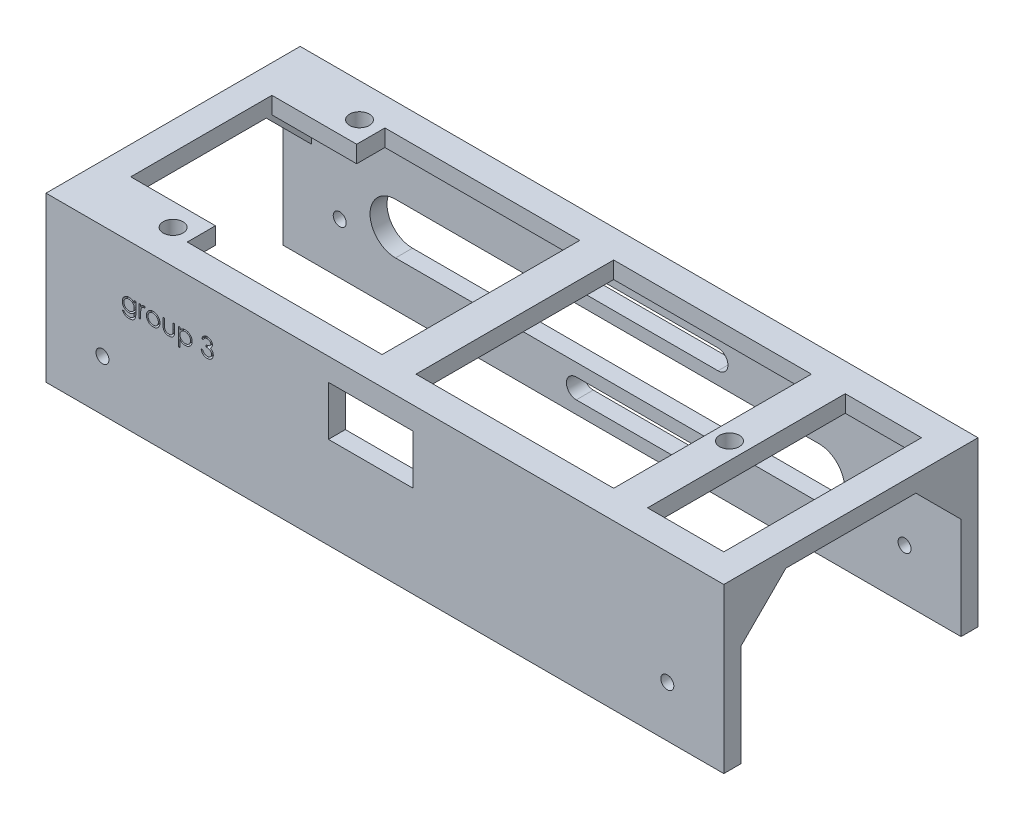
SolidWorks part; units mm, degrees
other "Markup1"
sketch "Sketch23" plane through (120, 29, 45) normal (0.0467, 0.9512, 0.3049) x (0.9885, 0, -0.1514)
sketch "Sketch24" plane through (120, 29, 45) normal (0.0467, 0.9512, 0.3049) x (0.9885, 0, -0.1514)
sketch "Sketch25" plane through (120, 29, 45) normal (0.0467, 0.9512, 0.3049) x (0.9885, 0, -0.1514)
sketch "Sketch26" plane through (120, 29, 45) normal (0.0467, 0.9512, 0.3049) x (0.9885, 0, -0.1514)
ref_plane "Front Plane" through (0, 0, 0) normal (0, 0, 1) x (1, 0, 0)
ref_plane "Top Plane" through (0, 0, 0) normal (0, 1, 0) x (1, 0, 0)
ref_plane "Right Plane" through (0, 0, 0) normal (1, 0, 0) x (0, 0, -1)
sketch "Sketch1" plane through (0, 0, 0) normal (0, 0, 1) x (1, 0, 0)
  line L9 (21.172, -17.9478) -> (91.172, -17.9478)
  line L10 (21.172, -17.9478) -> (21.172, -40.3878)
  line L11 (4, -8) -> (200.227, -8) construction
  line L12 (4, -8) -> (-67.5185, -8) construction
  line L13 (21.172, -40.3878) -> (91.172, -40.3878)
  line L14 (91.172, -17.9478) -> (91.172, -40.3878)
  line L15 (0, 0) -> (120, 0)
  line L16 (0, 0) -> (0, 29)
  line L17 (0, 29) -> (120, 29)
  line L18 (120, 0) -> (120, 29)
  circle A0 centre (4, 7) radius 1.15
  circle A1 centre (4, 7) radius 15 construction
  circle A3 centre (77.172, -29.1678) radius 3.6067
  circle A4 centre (116, 7) radius 15 construction
  circle A5 centre (116, 7) radius 1.15
  point P19 (21.172, -29.1678)
  dimension "D4" = 30
  dimension "D2" = 14
  dimension "D7" = 30
  dimension "D11" = 4
  dimension "D13" = 2.3
  dimension "D14" = 2.3
  dimension "D3" = 70
  dimension "D5" = 22.44
  dimension "D6" = 120
  dimension "D8" = 29
  dimension "D9" = 4
  dimension "D10" = 7
  dimension "D12" = 7
extrude "Boss-Extrude5" add sketch "Sketch1" along normal blind 45 contours L16 L15 L18 L17
shell "Shell9" thickness 3 removed face at (120, 14.5, 22.5) removed face at (60, 0, 22.5) removed face at (0, 14.5, 22.5)
sketch "Sketch3" plane through (0, 0, 0) normal (0, 0, -1) x (-1, 0, 0)
  line L0 (0, 0) -> (-120, 0) construction
  line L1 (-120, 0) -> (-120, 29) construction
  line L2 (0, 0) -> (0, 29) construction
  circle A0 centre (-10, 9) radius 1.15
  circle A1 centre (-110, 9) radius 1.15
  dimension "D1" = 2.3
  dimension "D2" = 2.3
  dimension "D3" = 9
  dimension "D4" = 10
  dimension "D5" = 9
  dimension "D6" = 10
extrude "Cut-Extrude2" cut sketch "Sketch3" against normal blind 79
sketch "Sketch6" plane through (0, 0, 0) normal (0, 0, -1) x (-1, 0, 0)
  line L0 (-76.9735, 21) -> (-51.8835, 21) construction
  line L1 (-76.9735, 22.75) -> (-51.8835, 22.75)
  line L2 (-76.9735, 19.25) -> (-51.8835, 19.25)
  line L7 (41.5249, -18.7743) -> (41.5249, -41.2143) construction
  line L8 (-94.8735, 12.5) -> (-19.8735, 12.5) construction
  line L9 (-94.8735, 17) -> (-19.8735, 17)
  line L10 (-94.8735, 8) -> (-19.8735, 8)
  line L11 (-19.8735, 12.5) -> (-17.326, 12.5) construction
  line L12 (-76.9735, 4) -> (-51.8835, 4) construction
  line L13 (-76.9735, 2.25) -> (-51.8835, 2.25)
  line L14 (-76.9735, 5.75) -> (-51.8835, 5.75)
  line L15 (4.7849, -29.9943) -> (74.7849, -29.9943) construction
  line L20 (4.7849, -18.7743) -> (74.7849, -18.7743)
  line L21 (4.7849, -18.7743) -> (4.7849, -41.2143)
  line L22 (4.7849, -41.2143) -> (74.7849, -41.2143)
  line L23 (74.7849, -18.7743) -> (74.7849, -41.2143)
  line L24 (-120, 0) -> (-120, 29) construction
  line L25 (63.3749, -18.7743) -> (63.3749, -41.2143) construction
  line L26 (0, 29) -> (-120, 29) construction
  arc A4 (-94.8735, 17) -> (-94.8735, 8) centre (-94.8735, 12.5) ccw
  arc A5 (-76.9735, 22.75) -> (-76.9735, 19.25) centre (-76.9735, 21) ccw
  arc A6 (-51.8835, 19.25) -> (-51.8835, 22.75) centre (-51.8835, 21) ccw
  arc A7 (-19.8735, 8) -> (-19.8735, 17) centre (-19.8735, 12.5) ccw
  arc A8 (-76.9735, 2.25) -> (-76.9735, 5.75) centre (-76.9735, 4) cw
  arc A9 (-51.8835, 5.75) -> (-51.8835, 2.25) centre (-51.8835, 4) cw
  circle A15 centre (16.1349, -29.9943) radius 1.5
  circle A16 centre (36.3249, -21.4943) radius 1.5
  circle A17 centre (36.3249, -38.4943) radius 1.5
  circle A18 centre (36.3249, -38.4943) radius 1.5
  circle A19 centre (27.0349, -29.9943) radius 2.3201
  point P11 (-64.4285, 21)
  point P19 (-57.3735, 12.5)
  point P31 (-64.4285, 4)
  dimension "D8" = 1.75
  dimension "D13" = 4.5
  dimension "D10" = 3
  dimension "D14" = 3
  dimension "D9" = 25.09
  dimension "D2" = 8.5
  dimension "D3" = 17.9
  dimension "D4" = 70
  dimension "D5" = 22.44
  dimension "D6" = 36.74
  dimension "D7" = 11.35
  dimension "D11" = 5.2
  dimension "D12" = 8.5
  dimension "D15" = 22.25
  dimension "D16" = 75
  dimension "D17" = 25.1265
  dimension "D18" = 11.41
  dimension "D19" = 16.5
extrude "Cut-Extrude8" cut sketch "Sketch6" against normal blind 23 contours L10 A7 L9 | L2 A6 L1 A5 | L13 A9 L14 A8 region at (64.4285, 21, 0) region at (57.3735, 12.5, 0)
sketch "Sketch7" plane through (0, 0, 45) normal (0, 0, 1) x (1, 0, 0)
  line L1 (50, 25) -> (65, 25)
  line L2 (50, 25) -> (50, 16.25)
  line L3 (50, 16.25) -> (65, 16.25)
  line L4 (65, 25) -> (65, 16.25)
  line L5 (0, 0) -> (120, 0) construction
  line L7 (0, 0) -> (0, 29) construction
  dimension "D1" = 50
  dimension "D2" = 15
  dimension "D3" = 8.75
  dimension "D4" = 25
extrude "Cut-Extrude9" cut sketch "Sketch7" against normal blind 20
sketch "Sketch13" plane through (0, 29, 0) normal (0, 1, 0) x (1, 0, 0)
  line L1 (0, 0) -> (120, 0) construction
  line L4 (5, -5) -> (115, -5)
  line L5 (5, -5) -> (5, -40)
  line L6 (5, -40) -> (115, -40)
  line L8 (0, -45) -> (0, 0) construction
  line L16 (115, -5) -> (115, -40)
  line L17 (120, -45) -> (120, 0) construction
  dimension "D1" = 5
  dimension "D2" = 5
  dimension "D5" = 5
  dimension "D6" = 35
extrude "Cut-Extrude14" cut sketch "Sketch13" against normal blind 10
sketch "Sketch17" plane through (0, 29, 0) normal (0, 1, 0) x (1, 0, 0)
  line L0 (0, -22.5) -> (120, -22.5) construction
  line L1 (5, -5) -> (20, -5)
  line L2 (5, -5) -> (5, -10)
  line L3 (5, -10) -> (20, -10)
  line L4 (20, -5) -> (20, -10)
  line L5 (5, -40) -> (20, -40)
  line L6 (5, -40) -> (5, -35)
  line L7 (5, -35) -> (20, -35)
  line L8 (20, -40) -> (20, -35)
  line L17 (0, -45) -> (0, 0) construction
  line L18 (120, -45) -> (120, 0) construction
  line L25 (115, -5) -> (5, -5) construction
  line L26 (95.5, -5) -> (101.5, -5)
  line L27 (95.5, -5) -> (95.5, -40)
  line L28 (95.5, -40) -> (101.5, -40)
  line L29 (101.5, -5) -> (101.5, -40)
  line L30 (5, -40) -> (115, -40) construction
  line L32 (54.5, -5) -> (60.5, -5)
  line L33 (54.5, -5) -> (54.5, -40)
  line L34 (54.5, -40) -> (60.5, -40)
  line L35 (60.5, -5) -> (60.5, -40)
  circle A0 centre (16.5, -39) radius 1.75
  circle A1 centre (16.5, -6) radius 1.75
  circle A2 centre (98.5, -22.5) radius 1.75
  point P41 (98.5, -5)
  line M10 (5, -40) -> (5, -5)
  line M11 (5, -5) -> (115, -5)
  line M13 (115, -40) -> (5, -40)
  dimension "D3" = 3.5
  dimension "D6" = 3.5
  dimension "D11" = 33
  dimension "D12" = 16.5
  dimension "D13" = 3.5
  dimension "D1" = 5
  dimension "D2" = 15
  dimension "D4" = 5
  dimension "D5" = 15
  dimension "D7" = 6
  dimension "D8" = 18.5
  dimension "D9" = 6
  dimension "D10" = 35
extrude "Boss-Extrude6" add sketch "Sketch17" against normal blind 3 contours A1 L3 L4 M11 M10 | L1 A1 | A0 L8 L7 M13 M10 | L5 A0 | L33 L32 L35 L34 | L27 L26 L29 L28 region at (12.0151, 29, 7.6523) region at (16.5, 29, 6.2435) region at (12.0151, 29, 37.3477) region at (16.5, 29, 38.7565)
extrude "Cut-Extrude16" cut sketch "Sketch17<4>" against normal blind 10 contours A2 L0 | L0 A2 | L1 A1 | L1 A1 | L5 A0 | L5 A0 | A2 region at (98.5, 29, 21.7573) region at (98.5, 29, 23.2427) region at (16.5, 29, 4.6937) region at (16.5, 29, 6.2435) region at (16.5, 29, 38.7565) region at (16.5, 29, 40.3063)
sketch "Sketch17<4>" plane through (0, 29, 0) normal (0, 1, 0) x (1, 0, 0) same geometry as "Sketch17"
sketch "Sketch20" plane through (0, 0, 45) normal (0, 0, 1) x (1, 0, 0)
  line L0 (13.2558, 18.0126) -> (38.9246, 18.0126) construction
  text T0 "group 3"
extrude "Cut-Extrude15" cut sketch "Sketch20" against normal blind 1.5
sketch "Sketch21" plane through (0, 0, 0) normal (-1, 0, 0) x (0, 0, 1)
  line L0 (3, 26) -> (3, 18)
  line L1 (3, 0) -> (3, 26) construction
  line L2 (3, 18) -> (11, 26)
  line L3 (42, 26) -> (3, 26) construction
  line L4 (11, 26) -> (3, 26)
  line L5 (42, 26) -> (34, 26)
  line L6 (34, 26) -> (42, 18)
  line L7 (42, 0) -> (42, 26) construction
  line L8 (42, 18) -> (42, 26)
  dimension "D1" = 8
  dimension "D2" = 8
  dimension "D3" = 8
  dimension "D4" = 8
extrude "Boss-Extrude7" add sketch "Sketch21" against normal blind 5
sketch "Sketch22" plane through (120, 0, 0) normal (1, 0, 0) x (0, 0, -1)
  line L0 (-42, 26) -> (-42, 18)
  line L1 (-42, 18) -> (-34, 26)
  line L2 (-34, 26) -> (-42, 26)
  line L3 (-11, 26) -> (-3, 26)
  line L4 (-3, 26) -> (-3, 18)
  line L5 (-3, 18) -> (-11, 26)
extrude "Boss-Extrude8" add sketch "Sketch22" against normal blind 5
equation "\"slot­_width\"=25.09"
equation "\"D9@Sketch6\"=\"slot­_width\""
